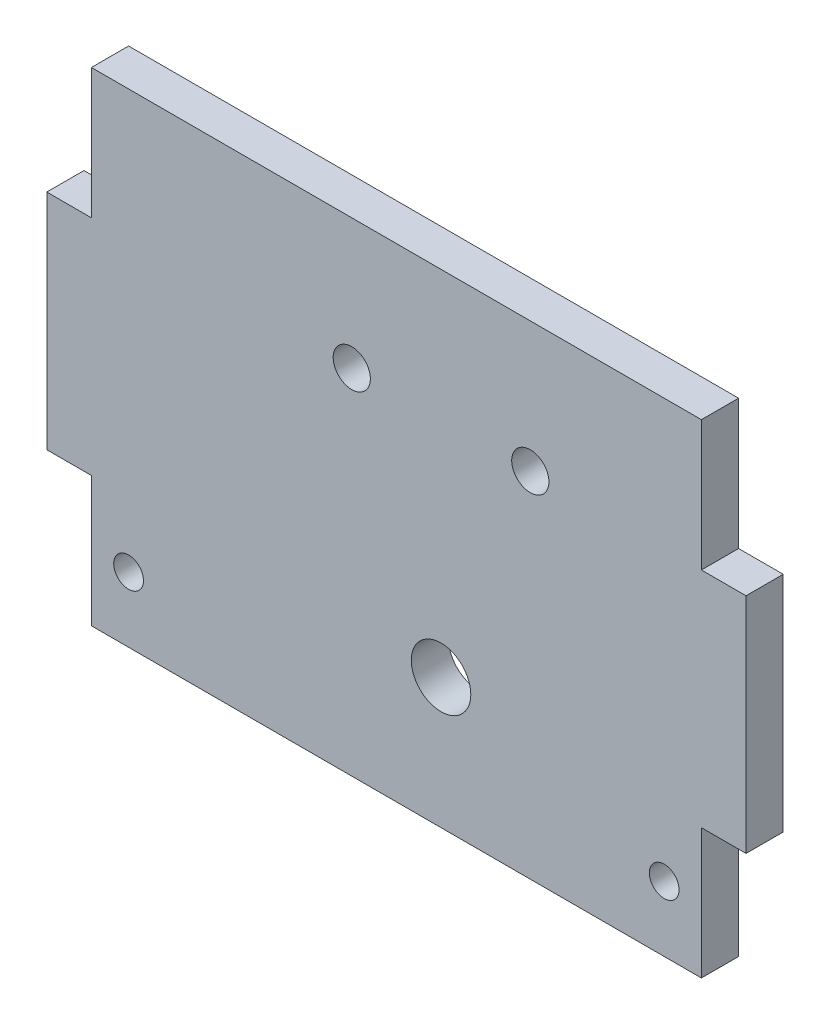
SolidWorks part; units mm, degrees
ref_plane "Front Plane" through (0, 0, 0) normal (0, 0, 1) x (1, 0, 0)
ref_plane "Top Plane" through (0, 0, 0) normal (0, 1, 0) x (1, 0, 0)
ref_plane "Right Plane" through (0, 0, 0) normal (1, 0, 0) x (0, 0, -1)
sketch "Sketch2" plane through (0, 0, 0) normal (0, 0, 1) x (1, 0, 0)
  line L1 (0, 0) -> (50, 0)
  line L2 (0, 0) -> (0, 65)
  line L3 (0, 65) -> (50, 65)
  line L4 (50, 0) -> (50, 65)
  circle A19 centre (25, 59.5) radius 2
  circle A20 centre (13, 47.5) radius 2
  circle A21 centre (37, 47.5) radius 2
  circle A23 centre (25, 17.5) radius 4
extrude "Boss-Extrude1" add sketch "Sketch2" along normal blind 5
sketch "Sketch3" plane through (0, 0, 5) normal (0, 0, 1) x (1, 0, 0)
  line L0 (0, 65) -> (-21, 65)
  line L1 (-21, 65) -> (-21, 0)
  line L2 (-21, 0) -> (0, 0)
  line L3 (0, 65) -> (0, 0)
extrude "Boss-Extrude2" add sketch "Sketch3" against normal up to surface (5 mm away) up to face at (15, 47.5, 0)
sketch "Sketch4" plane through (0, 0, 5) normal (0, 0, 1) x (1, 0, 0)
  line L0 (-21, 65) -> (-22, 65)
  line L1 (-22, 65) -> (-22, 0)
  line L2 (-22, 0) -> (-21, 0)
  line L3 (-21, 0) -> (-21, 65)
extrude "Boss-Extrude3" add sketch "Sketch4" against normal up to surface (5 mm away) up to face at (15, 47.5, 0)
sketch "Sketch5" plane through (0, 0, 5) normal (0, 0, 1) x (1, 0, 0)
  line L0 (-22, 32.5) -> (-22, 47.5)
  line L1 (-22, 65) -> (-22, 0) construction
  line L2 (-22, 32.5) -> (-22, 17.5)
  line L3 (-22, 17.5) -> (-28, 17.5)
  line L4 (-28, 17.5) -> (-28, 47.5)
  line L5 (-28, 47.5) -> (-22, 47.5)
  line L6 (50, 65) -> (-22, 65) construction
  line L7 (14, 65) -> (14, 8.5351)
  line L8 (56, 47.5) -> (50, 47.5)
  line L9 (56, 17.5) -> (56, 47.5)
  line L10 (50, 17.5) -> (56, 17.5)
  line L11 (50, 32.5) -> (50, 17.5)
  line L12 (50, 32.5) -> (50, 47.5)
  line M8 (-22, 65) -> (-22, 0)
  line M10 (50, 0) -> (50, 65)
extrude "Boss-Extrude4" add sketch "Sketch5" against normal up to surface (5 mm away) contours L5 L4 L3 M8 | L10 L9 L8 M10 region at (-25, 32.5, 5) region at (53, 32.5, 5) up to face at (15, 47.5, 0)
sketch "Sketch6" plane through (0, 0, 5) normal (0, 0, 1) x (1, 0, 0)
  circle A1 centre (25, 35.5) radius 2
extrude "Cut-Extrude1" cut sketch "Sketch6" against normal blind 59
sketch "Sketch7" plane through (0, 0, 5) normal (0, 0, 1) x (1, 0, 0)
  line L0 (-22, 47.5) -> (-22, 65)
  line L1 (-22, 56.25) -> (-17, 56.25)
  line L2 (14, 65) -> (14, 56.25)
  line L3 (50, 65) -> (-22, 65) construction
  line L4 (-28, 32.5) -> (-15.3264, 32.5)
  line L5 (-28, 17.5) -> (-28, 47.5) construction
  circle A0 centre (-17, 56.25) radius 1.5
  circle A1 centre (45, 56.25) radius 1.5
  circle A2 centre (45, 8.75) radius 1.5
  circle A3 centre (-17, 8.75) radius 1.5
extrude "Cut-Extrude2" cut sketch "Sketch7" against normal blind 10 contours A0 | A1 region at (-17, 54.7924, 5) region at (45, 56.25, 5)
extrude "Cut-Extrude3" cut sketch "Sketch7<4>" against normal blind 10 contours A2 | A3 region at (45, 8.75, 5)
sketch "Sketch7<4>" plane through (0, 0, 5) normal (0, 0, 1) x (1, 0, 0) same geometry as "Sketch7"
extrude "Boss-Extrude5" add sketch "Sketch7<5>" against normal up to surface (5 mm away) contours A0 | A1 region at (-17, 54.7924, 5) region at (45, 56.25, 5) up to face at (-18.5, 8.75, 0)
sketch "Sketch7<5>" plane through (0, 0, 5) normal (0, 0, 1) x (1, 0, 0) same geometry as "Sketch7"
sketch "Sketch8" plane through (0, 0, 5) normal (0, 0, 1) x (1, 0, 0)
  circle A0 centre (-17, 8.75) radius 2
  circle A1 centre (45, 8.75) radius 2
extrude "Cut-Extrude4" cut sketch "Sketch8" against normal blind 10
sketch "Sketch9" plane through (0, 0, 5) normal (0, 0, 1) x (1, 0, 0)
  circle A0 centre (25, 59.5) radius 2.5
  circle A1 centre (25, 35.5) radius 2.5
  circle A2 centre (13, 47.5) radius 2.5
  circle A3 centre (37, 47.5) radius 2.5
extrude "Cut-Extrude5" cut sketch "Sketch9" against normal blind 10
sketch "Sketch10" plane through (0, 0, 5) normal (0, 0, 1) x (1, 0, 0)
  line L0 (13, 47.5) -> (37, 47.5)
  line L1 (25, 47.5) -> (43.5, 47.5)
  line L2 (25, 47.5) -> (6.5, 47.5)
  circle A0 centre (13, 47.5) radius 2.5
  circle A1 centre (25, 59.5) radius 2.5
  circle A2 centre (37, 47.5) radius 2.5
  circle A3 centre (25, 35.5) radius 2.5
  circle A4 centre (6.5, 47.5) radius 2.5
  circle A5 centre (43.5, 47.5) radius 2.5
  circle M2 centre (25, 59.5) radius 2.5
  circle M3 centre (25, 35.5) radius 2.5
  circle M4 centre (13, 47.5) radius 2.5
  circle M5 centre (37, 47.5) radius 2.5
extrude "Boss-Extrude6" add sketch "Sketch10" against normal up to surface (5 mm away) contours L2 L0 M4 | L0 L2 M4 | M2 | L0 L1 M5 | L1 L0 M5 | M3 region at (13, 48.561, 5) region at (13, 46.439, 5) region at (37, 48.561, 5) region at (37, 46.439, 5) region at (25, 59.5, 5) region at (25, 35.5, 5) up to face at (22.5, 59.5, 0)
extrude "Cut-Extrude6" cut sketch "Sketch10<4>" against normal blind 10 contours A4 | A5 region at (43.5, 49.9293, 5) region at (4.0707, 47.5, 5)
sketch "Sketch10<4>" plane through (0, 0, 5) normal (0, 0, 1) x (1, 0, 0) same geometry as "Sketch10"
sketch "Sketch11" plane through (0, 65, 0) normal (0, 1, 0) x (1, 0, 0)
  line L1 (-22, 0) -> (50, 0)
  line L2 (-22, 0) -> (-22, -5)
  line L3 (-22, -5) -> (50, -5)
  line L4 (50, 0) -> (50, -5)
extrude "Boss-Extrude7" add sketch "Sketch11" along normal blind 10
sketch "Sketch12" plane through (50, 0, 0) normal (1, 0, 0) x (0, 0, -1)
  line L1 (-5, 17.5) -> (0, 17.5)
  line L2 (-5, 17.5) -> (-5, 0)
  line L3 (-5, 0) -> (0, 0)
  line L4 (0, 17.5) -> (0, 0)
sketch "Sketch13" plane through (56, 0, 0) normal (1, 0, 0) x (0, 0, -1)
  line L1 (-5, 47.5) -> (0, 47.5)
  line L2 (-5, 47.5) -> (-5, 17.5)
  line L3 (-5, 17.5) -> (0, 17.5)
  line L4 (0, 47.5) -> (0, 17.5)
sketch "Sketch14" plane through (50, 0, 0) normal (1, 0, 0) x (0, 0, -1)
  line L1 (-5, 75) -> (0, 75)
  line L2 (-5, 75) -> (-5, 47.5)
  line L3 (-5, 47.5) -> (0, 47.5)
  line L4 (0, 75) -> (0, 47.5)
extrude "Boss-Extrude8" add sketch "Sketch12" along normal blind 10
extrude "Boss-Extrude9" add sketch "Sketch14" along normal blind 10
extrude "Boss-Extrude10" add sketch "Sketch13" along normal blind 10
sketch "Sketch17" plane through (0, 0, 5) normal (0, 0, 1) x (1, 0, 0)
  line L0 (45, 8.75) -> (55, 8.75)
  circle A0 centre (45, 8.75) radius 2
  circle A1 centre (55, 8.75) radius 2
  circle M17 centre (45, 8.75) radius 2
extrude "Boss-Extrude11" add sketch "Sketch17" against normal up to surface (5 mm away) contours M17 region at (43.0566, 8.75, 5) up to face at (19, 34.1667, 0)
extrude "Cut-Extrude7" cut sketch "Sketch17<3>" against normal blind 10 contours A1 region at (55, 10.6934, 5)
sketch "Sketch17<3>" plane through (0, 0, 5) normal (0, 0, 1) x (1, 0, 0) same geometry as "Sketch17"
sketch "Sketch18" plane through (0, 75, 0) normal (0, 1, 0) x (1, 0, 0)
  line L1 (60, 0) -> (-22, 0)
  line L2 (60, 0) -> (60, -5)
  line L3 (60, -5) -> (-22, -5)
  line L4 (-22, 0) -> (-22, -5)
extrude "Cut-Extrude8" cut sketch "Sketch18" against normal blind 10
sketch "Sketch19" plane through (0, 0, 5) normal (0, 0, 1) x (1, 0, 0)
  line L0 (6.5, 47.5) -> (43.5, 47.5)
  line L1 (25, 47.5) -> (13, 47.5)
  line L2 (25, 47.5) -> (37, 47.5)
  circle A0 centre (6.5, 47.5) radius 2.5
  circle A1 centre (13, 47.5) radius 2.5
  circle A2 centre (37, 47.5) radius 2.5
  circle A3 centre (43.5, 47.5) radius 2.5
  circle M14 centre (6.5, 47.5) radius 2.5
  circle M15 centre (43.5, 47.5) radius 2.5
extrude "Boss-Extrude12" add sketch "Sketch19" against normal up to surface (5 mm away) contours M14 | M15 region at (43.5, 49.9293, 5) region at (4.0707, 47.5, 5) up to face at (19, 32.5, 0)
extrude "Cut-Extrude9" cut sketch "Sketch19<3>" against normal blind 10 contours L0 A1 | L0 A1 | L0 A2 L2 | L2 A2 L0 region at (13, 48.561, 5) region at (13, 46.439, 5) region at (37, 48.561, 5) region at (37, 46.439, 5)
sketch "Sketch19<3>" plane through (0, 0, 5) normal (0, 0, 1) x (1, 0, 0) same geometry as "Sketch19"
